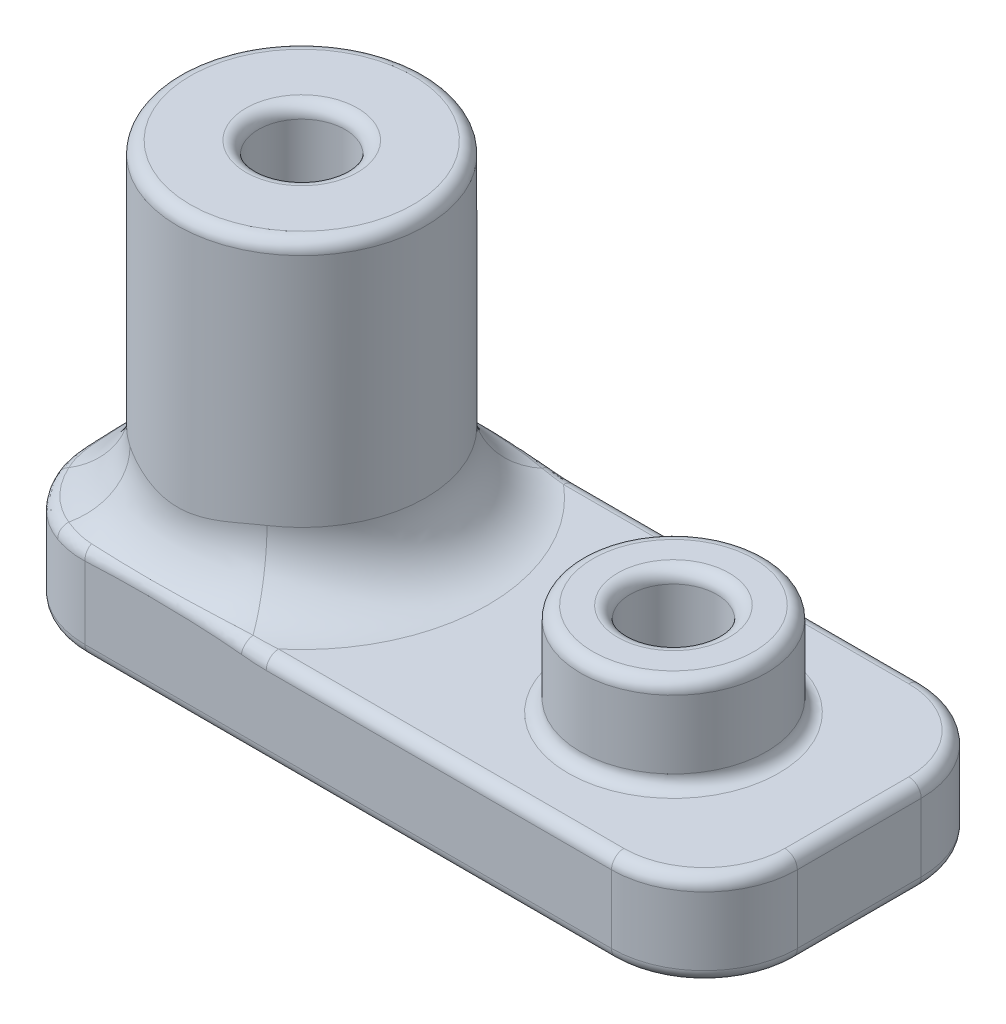
SolidWorks part; units mm, degrees
ref_plane "Front Plane" through (0, 0, 0) normal (0, 0, 1) x (1, 0, 0)
ref_plane "Top Plane" through (0, 0, 0) normal (0, 1, 0) x (1, 0, 0)
ref_plane "Right Plane" through (0, 0, 0) normal (1, 0, 0) x (0, 0, -1)
sketch "Sketch1" plane through (0, 0, 0) normal (0, 1, 0) x (1, 0, 0)
  line L1 (0, 0) -> (23, 0)
  line L2 (0, 0) -> (0, -10)
  line L3 (0, -10) -> (23, -10)
  line L4 (23, 0) -> (23, -10)
  dimension "D1" = 10
  dimension "D2" = 23
extrude "Boss-Extrude1" add sketch "Sketch1" along normal blind 3
sketch "Sketch2" plane through (0, 3, 0) normal (0, 1, 0) x (1, 0, 0)
  line L0 (23, 0) -> (0, 0) construction
  line L1 (0, 0) -> (0, -10) construction
  circle A0 centre (5, -5) radius 4
  dimension "D1" = 8
  dimension "D2" = 5
  dimension "D3" = 5
extrude "Boss-Extrude2" add sketch "Sketch2" along normal blind 10
sketch "Sketch3" plane through (0, 13, 0) normal (0, 1, 0) x (1, 0, 0)
  circle A0 centre (5, -5) radius 1.4
  dimension "D1" = 2.8
extrude "Cut-Extrude1" cut sketch "Sketch3" against normal through all
sketch "Sketch4" plane through (0, 3, 0) normal (0, 1, 0) x (1, 0, 0)
  line L5 (23, -10) -> (23, 0) construction
  circle A0 centre (17, -5) radius 1.4
  circle A1 centre (5, -5) radius 4 construction
  point P4 (23, -5)
  dimension "D1" = 0
  dimension "D3" = 2.8
  dimension "D2" = 12
extrude "Cut-Extrude2" cut sketch "Sketch4" against normal through all
sketch "Sketch6" plane through (0, 3, 0) normal (0, 1, 0) x (1, 0, 0)
  circle A0 centre (17, -5) radius 1.4
  circle A1 centre (17, -5) radius 3
  dimension "D1" = 6
  dimension "D2" = 2.8
extrude "Boss-Extrude3" add sketch "Sketch6" along normal blind 3
fillet "Fillet1" radius 2 1 edges at (5, 3, 9)
fillet "Fillet3" radius 3 4 edges at (23, 1.5, 10) (23, 1.5, 0) (0, 1.5, 10) (0, 1.5, 0)
fillet "Fillet4" radius 0.4 20 edges at (5.6583, 3, 10) (2.8279, 3.0015, 9.9951) (2, 3.0218, 0.1716) (5.6583, 3, 0) (22.1213, 0, 0.8787) (11.5, 0, 0) (0.8787, 0, 0.8787) (0, 0, 5) (0.8787, 0, 9.1213) (11.5, 0, 10) (22.1213, 0, 9.1213) (23, 0, 5) (5, 0, 6.4) (14.1583, 3, 0) (22.1213, 3, 0.8787) (23, 3, 5) (22.1213, 3, 9.1213) (14.1583, 3, 10) (17, 0, 6.4) (17, 3, 8)
fillet "Fillet5" radius 0.4 4 edges at (5, 13, 9) (5, 13, 6.4) (17, 6, 6.4) (17, 6, 8)
